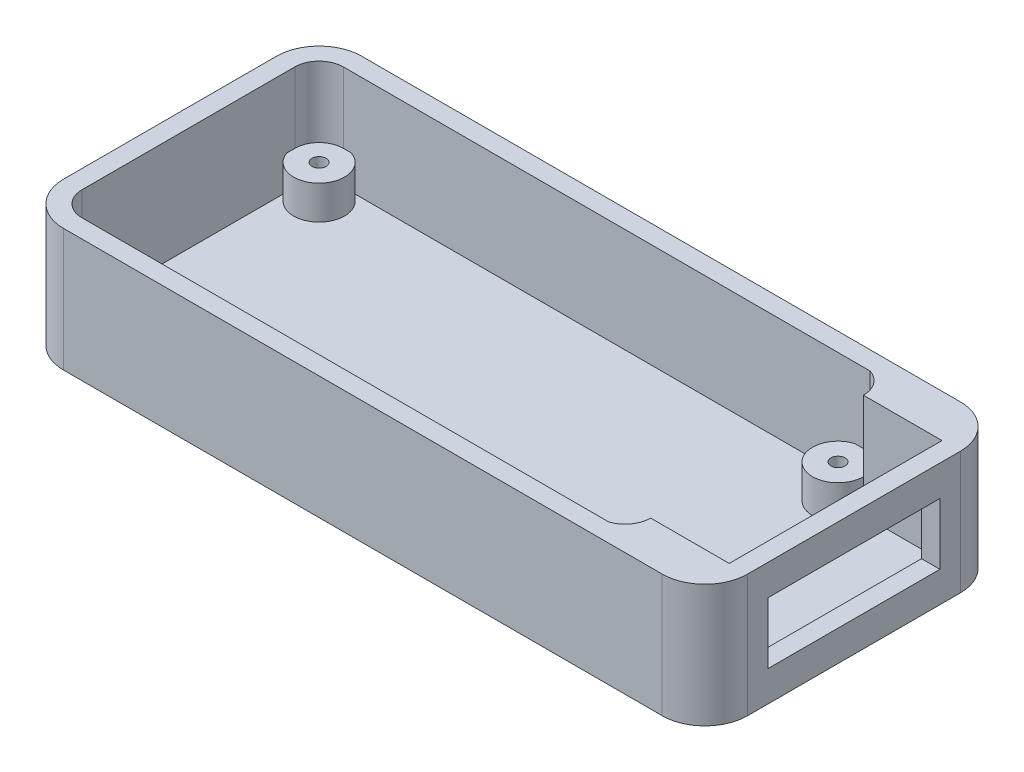
SolidWorks part; units mm, degrees
ref_plane "前视基准面" through (0, 0, 0) normal (0, 0, 1) x (1, 0, 0)
ref_plane "上视基准面" through (0, 0, 0) normal (0, 1, 0) x (1, 0, 0)
ref_plane "右视基准面" through (0, 0, 0) normal (1, 0, 0) x (0, 0, -1)
other "Configuration Table"
sketch "草图3" plane through (0, 0, 0) normal (0, 1, 0) x (1, 0, 0)
  line L0 (1.7812, 0.127) -> (50.5671, 0.127) construction
  line L1 (45.8471, 1.9057) -> (45.8471, 19.2501) construction
  line L2 (50.5671, 21.0287) -> (1.7812, 21.0287) construction
  line L3 (0.0025, 19.2501) -> (0.0025, 1.9057) construction
  line L4 (52.3471, 1.907) -> (52.3471, 19.2487) construction
  line L5 (52.3471, 1.9057) -> (52.3471, 19.2501) construction
  line L6 (50.5671, 21.2287) -> (1.7812, 21.2287)
  line L7 (-0.1975, 19.2501) -> (-0.1975, 1.9057)
  line L8 (1.7812, -0.073) -> (50.5671, -0.073)
  line L9 (52.5471, 1.907) -> (52.5471, 19.2487)
  arc A0 (44.0684, 0.127) -> (45.8471, 1.9057) centre (44.0684, 1.9057) ccw construction
  arc A1 (45.8471, 19.2501) -> (44.0684, 21.0287) centre (44.0684, 19.2501) ccw construction
  arc A2 (1.7812, 21.0287) -> (0.0025, 19.2501) centre (1.7812, 19.2501) ccw construction
  arc A3 (0.0025, 1.9057) -> (1.7812, 0.127) centre (1.7812, 1.9057) ccw construction
  circle A4 centre (1.7805, 1.905) radius 0.5766
  circle A5 centre (44.0691, 1.905) radius 0.5766
  circle A6 centre (1.7805, 19.2507) radius 0.5766
  circle A7 centre (44.0691, 19.2507) radius 0.5766
  circle A8 centre (6.5527, 7.524) radius 0.35
  circle A9 centre (6.5527, 13.304) radius 0.35
  arc A10 (50.5671, 0.127) -> (52.3471, 1.907) centre (50.5671, 1.907) ccw construction
  arc A11 (52.3471, 19.2487) -> (50.5671, 21.0287) centre (50.5671, 19.2487) ccw construction
  arc A12 (1.7812, 21.2287) -> (-0.1975, 19.2501) centre (1.7812, 19.2501) ccw
  arc A13 (-0.1975, 1.9057) -> (1.7812, -0.073) centre (1.7812, 1.9057) ccw
  arc A14 (50.5671, -0.073) -> (52.5471, 1.907) centre (50.5671, 1.907) ccw
  arc A15 (52.5471, 19.2487) -> (50.5671, 21.2287) centre (50.5671, 19.2487) ccw
  dimension "D2" = 1.78
  dimension "D3" = 0.2
  dimension "D1" = 6.5
extrude "拉伸-薄壁4" add sketch "草图3" along normal blind 10 thin contours L6 A12 L7 A13 L8 A14 L9 A15 thin type one direction wall 1.5
extrude "凸台-拉伸3" add sketch "草图3<5>" along normal blind 1.5 contours L6 A12 L7 A13 L8 A14 L9 A15
sketch "草图3<5>" plane through (0, 0, 0) normal (0, 1, 0) x (1, 0, 0) same geometry as "草图3"
sketch "草图7" plane through (54.0471, 0, 0) normal (1, 0, 0) x (0, 0, -1)
  line L1 (10.5779, 9.8116) -> (10.5779, -4.218) construction
  line L3 (19.2501, 2.5) -> (1.9057, 2.5) construction
  line L5 (2.2506, 5) -> (18.6549, 5) construction
  line L6 (17.5779, 2.5) -> (3.5779, 2.5)
  line L7 (17.5779, 2.5) -> (17.5779, 7.5)
  line L8 (17.5779, 7.5) -> (3.5779, 7.5)
  line L9 (3.5779, 2.5) -> (3.5779, 7.5)
  line L10 (2.2506, 4.25) -> (18.6549, 4.25) construction
  line L11 (2.2506, 5.75) -> (18.6549, 5.75) construction
  line L12 (1.907, 10) -> (19.2487, 10) construction
  point P6 (10.5779, 2.5)
  point P18 (10.5779, 10)
  dimension "D2" = 14
  dimension "D3" = 5
extrude "切除-拉伸2" cut sketch "草图7" against normal up to next
ref_plane "基准面4" through (0, 4.25, 0) normal (0, 1, 0) x (1, 0, 0)
sketch "草图8" plane through (0, 1.5, 0) normal (0, 1, 0) x (1, 0, 0)
  circle A0 centre (44.0691, 1.905) radius 0.5766 construction
  circle A1 centre (44.0691, 19.2507) radius 0.5766 construction
  circle A2 centre (1.7805, 19.2507) radius 0.5766 construction
  circle A3 centre (1.7805, 1.905) radius 0.5766 construction
  circle A4 centre (44.0691, 1.905) radius 0.5766
  circle A5 centre (44.0691, 19.2507) radius 0.5766
  circle A6 centre (1.7805, 19.2507) radius 0.5766
  circle A7 centre (1.7805, 1.905) radius 0.5766
extrude "拉伸-薄壁5" add sketch "草图8" along normal up to surface (2.75 mm away) thin up to plane "基准面4" thin type one direction wall 1.5
sketch "草图9" plane through (0, 1.5, 0) normal (0, 1, 0) x (1, 0, 0)
  line L0 (44.7013, -0.073) -> (50.5671, -0.073) construction
  line L1 (44.7013, -0.073) -> (50.5671, -0.073)
  line L2 (52.5471, 1.907) -> (46.1457, 1.907)
  line L3 (54.9353, 10.5779) -> (-6.6715, 10.5779) construction
  line L4 (44.7013, 21.2287) -> (50.5671, 21.2287)
  line L5 (52.5471, 19.2487) -> (46.1457, 19.2487)
  arc A0 (44.7013, -0.073) -> (43.4369, -0.073) centre (44.0691, 1.905) ccw construction
  arc A1 (44.7013, -0.073) -> (46.1457, 1.907) centre (44.0691, 1.905) ccw
  arc A2 (50.5671, -0.073) -> (52.5471, 1.907) centre (50.5671, 1.907) ccw construction
  arc A3 (50.5671, -0.073) -> (52.5471, 1.907) centre (50.5671, 1.907) ccw
  arc A5 (50.5671, 21.2287) -> (52.5471, 19.2487) centre (50.5671, 19.2487) cw
  arc A6 (44.7013, 21.2287) -> (46.1457, 19.2487) centre (44.0691, 19.2507) cw
extrude "凸台-拉伸4" add sketch "草图9" along normal up to surface (8.5 mm away) up to face at (26.1745, 10, -10.5779)
sketch "草图11" plane through (-1.6975, 0, 0) normal (-1, 0, 0) x (0, 0, 1)
  line L0 (-14.8843, 6.8507) -> (-14.8843, 8.0506) construction
  line L1 (-1.9057, 0) -> (-1.9057, 10) construction
  line L2 (-1.9057, 10) -> (-19.2501, 10) construction
  line L3 (-19.2501, 10) -> (-19.2501, 0) construction
  line L4 (-5.945, 8.0506) -> (-5.945, 6.8507) construction
  line L5 (-13.8844, 9.0506) -> (-6.9449, 9.0506) construction
  line L6 (-13.8844, 5.8508) -> (-6.9449, 5.8508) construction
  line L7 (-19.2501, 0) -> (-1.9057, 0) construction
  line L8 (-10.5779, 12.8246) -> (-10.5779, -2.6873) construction
  line L9 (-15.8843, 6.8507) -> (-15.8843, 8.0506)
  line L10 (-4.945, 8.0506) -> (-4.945, 6.8507)
  line L11 (-15.2073, 5.3508) -> (-5.6221, 5.3508)
  line L12 (-15.2073, 9.5506) -> (-5.6221, 9.5506)
  line L13 (-13.8844, 9.5506) -> (-6.9449, 9.5506) construction
  line L14 (-13.8844, 5.3508) -> (-6.9449, 5.3508) construction
  arc A0 (-13.8844, 9.0506) -> (-14.8843, 8.0506) centre (-13.8844, 8.0506) ccw construction
  arc A1 (-6.9449, 5.8508) -> (-5.945, 6.8507) centre (-6.9449, 6.8507) ccw construction
  arc A2 (-5.945, 8.0506) -> (-6.9449, 9.0506) centre (-6.9449, 8.0506) ccw construction
  arc A3 (-14.8843, 6.8507) -> (-13.8844, 5.8508) centre (-13.8844, 6.8507) ccw construction
  arc A4 (-13.8844, 10.0506) -> (-14.3313, 10) centre (-13.8844, 8.0506) ccw
  arc A5 (-15.8843, 6.8507) -> (-15.2073, 5.3508) centre (-13.8844, 6.8507) ccw
  arc A6 (-5.6221, 5.3508) -> (-4.945, 6.8507) centre (-6.9449, 6.8507) ccw
  arc A7 (-4.945, 8.0506) -> (-5.6221, 9.5506) centre (-6.9449, 8.0506) ccw
  arc A8 (-15.2073, 9.5506) -> (-15.8843, 8.0506) centre (-13.8844, 8.0506) ccw
  arc A9 (-6.4981, 10) -> (-6.9449, 10.0506) centre (-6.9449, 8.0506) ccw
  arc A10 (-13.8844, 10.0506) -> (-15.8843, 8.0506) centre (-13.8844, 8.0506) ccw construction
  arc A12 (-4.945, 8.0506) -> (-6.9449, 10.0506) centre (-6.9449, 8.0506) ccw construction
  arc A13 (-6.9449, 4.8508) -> (-4.945, 6.8507) centre (-6.9449, 6.8507) ccw construction
  arc A14 (-15.8843, 6.8507) -> (-13.8844, 4.8508) centre (-13.8844, 6.8507) ccw construction
  point P16 (-14.8843, 7.4507)
  point P20 (-10.5779, 10)
  dimension "D3" = 0.9999
  dimension "D6" = 0.9999
  dimension "D7" = 0.9999
  dimension "D8" = 0.9999
  dimension "D1" = 5.8508
  dimension "D2" = 3.1998
  dimension "D4" = 4.0393
  dimension "D5" = 1.1999
  dimension "D9" = 1.1999
  dimension "D10" = 1
  dimension "D11" = 6.9395
  dimension "D12" = 1
  dimension "D13" = 0.5
  dimension "D14" = 0.5
